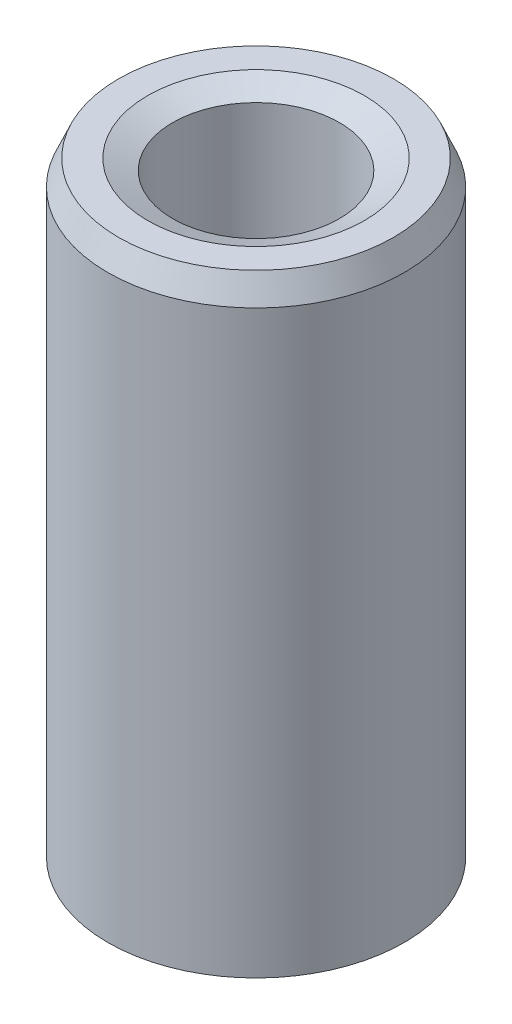
SolidWorks part; units mm, degrees
ref_plane "Front Plane" through (0, 0, 0) normal (0, 0, 1) x (1, 0, 0)
ref_plane "Top Plane" through (0, 0, 0) normal (0, 1, 0) x (1, 0, 0)
ref_plane "Right Plane" through (0, 0, 0) normal (1, 0, 0) x (0, 0, -1)
sketch "Sketch1" plane through (0, 0, 0) normal (0, 1, 0) x (1, 0, 0)
  circle A0 centre (0, 0) radius 22.5
  dimension "SLEEVE_OD" = 45
extrude "Boss-Extrude1" add sketch "Sketch1" along normal blind 93.4971
sketch "Sketch2" plane through (0, 0, 0) normal (0, 1, 0) x (1, 0, 0)
  circle A0 centre (0, 0) radius 12.6467
  dimension "BORE_D" = 25.2934
extrude "Cut-Extrude1" cut sketch "Sketch2" along normal through all
chamfer "Chamfer1" distance 3.7967 angle 23.399 4 edges at (0, 93.4971, 12.6467) (0, 0, 12.6467) (0, 0, 22.5) (0, 93.4971, 22.5) first distance on face at (0, 93.4971, 12.6467) first distance on face at (0, 0, 12.6467) first distance on face at (0, 93.4971, 22.5)
